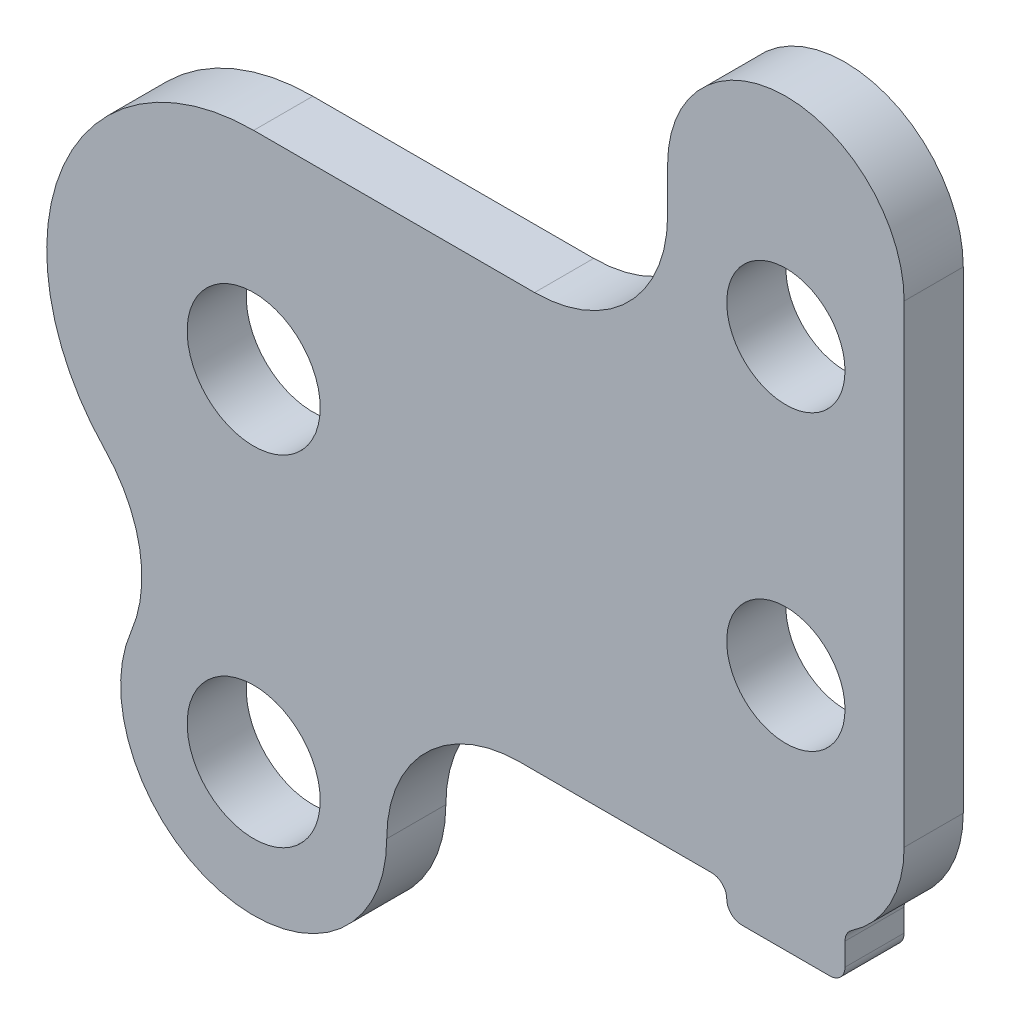
SolidWorks part; units mm, degrees
ref_plane "Front Plane" through (0, 0, 0) normal (0, 0, 1) x (1, 0, 0)
ref_plane "Top Plane" through (0, 0, 0) normal (0, 1, 0) x (1, 0, 0)
ref_plane "Right Plane" through (0, 0, 0) normal (1, 0, 0) x (0, 0, -1)
sketch "Sketch1" plane through (0, 0, 0) normal (0, 0, 1) x (1, 0, 0)
  line L2 (0, 5.5562) -> (0, -5.5562) construction
  line L6 (0, 5.5562) -> (0, -12.7) construction
  line L9 (17.4625, 13.4938) -> (11.1125, 13.4938)
  line L10 (11.1125, 13.4938) -> (11.1125, 5.5563)
  line L11 (17.4625, 13.4938) -> (17.4625, -5.5562)
  line L12 (17.4625, -5.5562) -> (0, -5.5562)
  line L13 (11.1125, 5.5563) -> (11.1125, -5.5563) construction
  line L14 (14.2875, 13.4938) -> (14.2875, -5.5563) construction
  line L15 (14.2875, 7.9058) -> (14.2875, 0.0318)
  line L16 (0, 5.5562) -> (11.1125, 5.5563)
  line L17 (15.875, -5.5563) -> (15.875, -5.1309)
  line L18 (12.7, -5.5563) -> (15.875, -5.5563)
  line L19 (12.7, -5.5563) -> (12.7, -6.3691)
  line L20 (12.7, -6.3691) -> (15.875, -6.3691)
  line L21 (15.875, -5.5563) -> (15.875, -6.3691)
  circle A0 centre (0, 0) radius 5.5562 construction
  arc A2 (0, 5.5562) -> (0, -5.5562) centre (0, 0) ccw
  circle A4 centre (0, 0) radius 1.7859
  circle A16 centre (14.2875, 7.9058) radius 1.5875
  circle A20 centre (14.2875, 0.0318) radius 1.5875
  circle A22 centre (0, 0) radius 12.7 construction
  circle A25 centre (0, 0) radius 9.1281 construction
  circle A29 centre (14.2875, 10.3188) radius 3.175
  circle A30 centre (14.2875, -2.3813) radius 3.175
  circle A32 centre (0, -9.1281) radius 3.5719
  circle A33 centre (0, -9.1281) radius 1.7859
  circle A34 centre (-6.5741, -6.3327) radius 3.5719
  circle A35 centre (7.1437, -9.1281) radius 3.5719
  point P17 (14.2875, -5.5563)
  point P20 (14.2875, 3.9688)
  dimension "D1" = 7.874
  dimension "D2" = 11.1125
  dimension "D3" = 3.5719
  dimension "D5" = 6.35
  dimension "D6" = 7.1437
  dimension "D8" = 3.175
  dimension "D9" = 0.8128
  dimension "D11" = 3.5719
  dimension "D4" = 19.05
  dimension "D10" = 3.175
extrude "Boss-Extrude1" add sketch "Sketch1" along normal blind 1.5875 contours A30 L15 A29 L10 L16 A2 L12 A4 | A2 | L16 L10 | A30 L11 A29 L15 | A29 A16 | A30 A20 | L16 | L21 L12 L18 L19 L20 | A30 L12 L17 | A32 A33 | A35 L12 A32 | L19 L18 L21 L20 region at (14.2875, 10.7962, 0) region at (16.1269, 3.9688, 0) region at (4.7017, 0.4223, 0) region at (14.2875, -2.8587, 0) region at (15.4836, -5.4303, 0) region at (14.2875, -5.9627, 0) region at (-2.4105, -5.669, 0) region at (3.5719, -6.3541, 0) region at (2.4543, -6.6739, 0)
fillet "Fillet1" radius 0.4064 4 edges at (15.875, -5.1309, 0.7937) (15.875, -6.3691, 0.7937) (12.7, -5.5562, 0.7937) (12.7, -6.3691, 0.7937)
fillet "Fillet2" radius 3.5719 1 edges at (11.1125, 5.5563, 0.7937)
